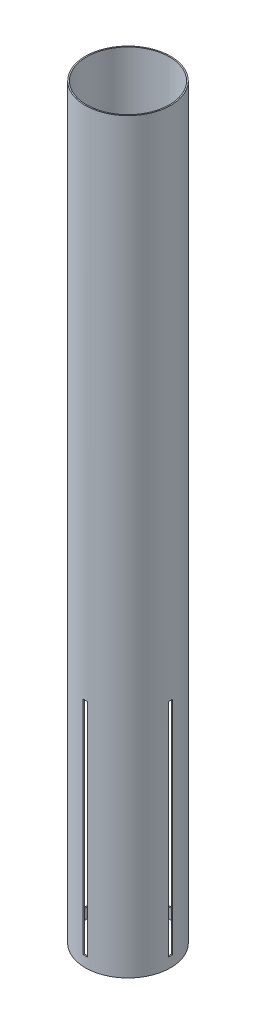
SolidWorks part; units mm, degrees
material "E-Glass Fiber"
ref_plane "Front Plane" through (0, 0, 0) normal (0, 0, 1) x (1, 0, 0)
ref_plane "Top Plane" through (0, 0, 0) normal (0, 1, 0) x (1, 0, 0)
ref_plane "Right Plane" through (0, 0, 0) normal (1, 0, 0) x (0, 0, -1)
sketch "Sustainer Tube Profile" plane through (0, 0, 0) normal (0, 1, 0) x (1, 0, 0)
  circle A0 centre (0, 0) radius 76.2
  circle A1 centre (0, 0) radius 78.359
  dimension "D1" = 152.4
  dimension "D2" = 156.718
extrude "Sustainer Tube Body" add sketch "Sustainer Tube Profile" along normal blind 1371.6
ref_plane "Plane1" through (0, 0, 78.359) normal (0, 0, 1) x (1, 0, 0)
sketch "Fin Slot Profile" plane through (0, 0, 78.359) normal (0, 0, 1) x (1, 0, 0)
  line L0 (0, 0) -> (0, 1371.6) construction
  line L5 (76.2, 1371.6) -> (-76.2, 1371.6) construction
  line L6 (-78.359, 0) -> (78.359, 0) construction
  line L7 (3.9688, 19.05) -> (-3.9688, 19.05)
  line L8 (0, 19.05) -> (0, 425.45)
  line L9 (3.9688, 425.45) -> (-3.9688, 425.45)
  line L10 (-3.9688, 19.05) -> (-3.9688, 425.45)
  line L11 (3.9688, 19.05) -> (3.9688, 425.45)
  dimension "D1" = 406.4
  dimension "D2" = 19.05
  dimension "D3" = 3.9688
extrude "Fin Slot Cut" cut sketch "Fin Slot Profile" against normal up to surface (2.2624 mm away) contours L7 L11 L9 L8 | L10 L7 L8 L9 region at (1.9844, 222.25, 78.359) region at (-1.9844, 222.25, 78.359) up to face at (0, 1371.6, 76.2)
pattern_circular "Fin Slot Pattern" count 4 over 360 about axis through (0, 1371.6, 0) along (0, 1, 0) of "Fin Slot Cut"
equation "\"Length\"= 54"
equation "\"Outer Diameter\"= 6.17"
equation "\"Inner Diameter\"= 6"
equation "\"Wall Thickness\"= 0.085"
equation "\"D1@Sustainer Tube Profile\" = \"Inner Diameter\""
equation "\"D2@Sustainer Tube Profile\" = \"Outer Diameter\""
equation "\"D1@Sustainer Tube Body\" = \"Length\""
equation "\"Root Chord\"= 16"
equation "\"Fin Offset\"= 3 / 4"
equation "\"D1@Fin Slot Profile\"=\"Root Chord\" "
equation "\"D2@Fin Slot Profile\" = \"Fin Offset\""
equation "\"Fin Thickness\" = ( 5 / 16 ) / 2"
equation "\"D3@Fin Slot Profile\"=\"Fin Thickness\""
